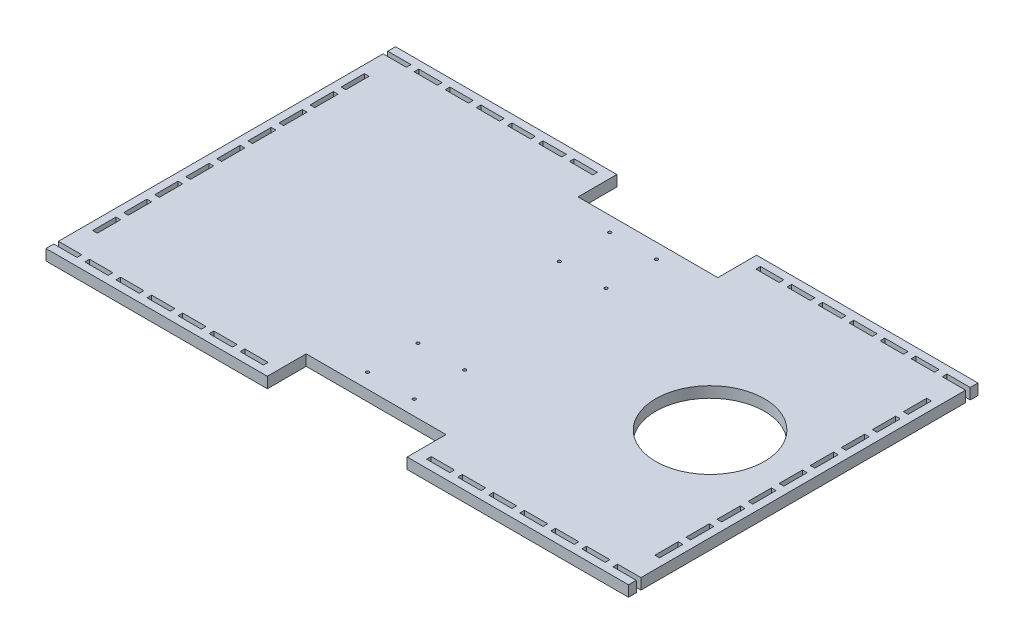
SolidWorks part; units mm, degrees
material "Thornel Mat VMA"
ref_plane "Front Plane" through (0, 0, 0) normal (0, 0, 1) x (1, 0, 0)
ref_plane "Top Plane" through (0, 0, 0) normal (0, 1, 0) x (1, 0, 0)
ref_plane "Right Plane" through (0, 0, 0) normal (1, 0, 0) x (0, 0, -1)
sketch "Sketch6" plane through (0, 0, 0) normal (0, 1, 0) x (1, 0, 0)
  line L0 (-187.5, 0) -> (187.5, 0) construction
  line L1 (-187.5, 112.5) -> (187.5, 112.5)
  line L2 (-187.5, 112.5) -> (-187.5, -112.5)
  line L3 (-187.5, -112.5) -> (187.5, -112.5)
  line L4 (187.5, 112.5) -> (187.5, -112.5)
  line L5 (0, -112.5) -> (0, -87.5) construction
  line L7 (187.5, -107.5) -> (172.5, -107.5)
  line L8 (187.5, -107.5) -> (187.5, -104.5)
  line L9 (187.5, -104.5) -> (172.5, -104.5)
  line L10 (172.5, -107.5) -> (172.5, -104.5)
  line L35 (187.5, 107.5) -> (172.5, 107.5)
  line L36 (187.5, 107.5) -> (187.5, 104.5)
  line L37 (187.5, 104.5) -> (172.5, 104.5)
  line L38 (172.5, 107.5) -> (172.5, 104.5)
  line L63 (-187.5, 104.5) -> (-172.5, 104.5)
  line L64 (-187.5, 104.5) -> (-187.5, 107.5)
  line L65 (-187.5, 107.5) -> (-172.5, 107.5)
  line L66 (-172.5, 104.5) -> (-172.5, 107.5)
  line L91 (-187.5, -107.5) -> (-172.5, -107.5)
  line L92 (-187.5, -107.5) -> (-187.5, -104.5)
  line L93 (-187.5, -104.5) -> (-172.5, -104.5)
  line L94 (-172.5, -107.5) -> (-172.5, -104.5)
  line L118 (167.5, 107.5) -> (152.5, 107.5)
  line L119 (152.5, 107.5) -> (152.5, 104.5)
  line L120 (167.5, 104.5) -> (152.5, 104.5)
  line L121 (167.5, 107.5) -> (167.5, 104.5)
  line L122 (167.5, -107.5) -> (152.5, -107.5)
  line L123 (152.5, -107.5) -> (152.5, -104.5)
  line L124 (167.5, -104.5) -> (152.5, -104.5)
  line L125 (167.5, -107.5) -> (167.5, -104.5)
  line L126 (147.5, 107.5) -> (132.5, 107.5)
  line L127 (132.5, 107.5) -> (132.5, 104.5)
  line L128 (147.5, 104.5) -> (132.5, 104.5)
  line L129 (147.5, 107.5) -> (147.5, 104.5)
  line L130 (147.5, -107.5) -> (132.5, -107.5)
  line L131 (132.5, -107.5) -> (132.5, -104.5)
  line L132 (147.5, -104.5) -> (132.5, -104.5)
  line L133 (147.5, -107.5) -> (147.5, -104.5)
  line L134 (127.5, 107.5) -> (112.5, 107.5)
  line L135 (112.5, 107.5) -> (112.5, 104.5)
  line L136 (127.5, 104.5) -> (112.5, 104.5)
  line L137 (127.5, 107.5) -> (127.5, 104.5)
  line L138 (127.5, -107.5) -> (112.5, -107.5)
  line L139 (112.5, -107.5) -> (112.5, -104.5)
  line L140 (127.5, -104.5) -> (112.5, -104.5)
  line L141 (127.5, -107.5) -> (127.5, -104.5)
  line L142 (107.5, 107.5) -> (92.5, 107.5)
  line L143 (92.5, 107.5) -> (92.5, 104.5)
  line L144 (107.5, 104.5) -> (92.5, 104.5)
  line L145 (107.5, 107.5) -> (107.5, 104.5)
  line L146 (107.5, -107.5) -> (92.5, -107.5)
  line L147 (92.5, -107.5) -> (92.5, -104.5)
  line L148 (107.5, -104.5) -> (92.5, -104.5)
  line L149 (107.5, -107.5) -> (107.5, -104.5)
  line L150 (87.5, 107.5) -> (72.5, 107.5)
  line L151 (72.5, 107.5) -> (72.5, 104.5)
  line L152 (87.5, 104.5) -> (72.5, 104.5)
  line L153 (87.5, 107.5) -> (87.5, 104.5)
  line L154 (87.5, -107.5) -> (72.5, -107.5)
  line L155 (72.5, -107.5) -> (72.5, -104.5)
  line L156 (87.5, -104.5) -> (72.5, -104.5)
  line L157 (87.5, -107.5) -> (87.5, -104.5)
  line L158 (67.5, 107.5) -> (52.5, 107.5)
  line L159 (52.5, 107.5) -> (52.5, 104.5)
  line L160 (67.5, 104.5) -> (52.5, 104.5)
  line L161 (67.5, 107.5) -> (67.5, 104.5)
  line L162 (67.5, -107.5) -> (52.5, -107.5)
  line L163 (52.5, -107.5) -> (52.5, -104.5)
  line L164 (67.5, -104.5) -> (52.5, -104.5)
  line L165 (67.5, -107.5) -> (67.5, -104.5)
  line L166 (-167.5, -107.5) -> (-152.5, -107.5)
  line L167 (-152.5, -107.5) -> (-152.5, -104.5)
  line L168 (-167.5, -104.5) -> (-152.5, -104.5)
  line L169 (-167.5, -107.5) -> (-167.5, -104.5)
  line L170 (-167.5, 104.5) -> (-152.5, 104.5)
  line L171 (-152.5, 104.5) -> (-152.5, 107.5)
  line L172 (-167.5, 107.5) -> (-152.5, 107.5)
  line L173 (-167.5, 104.5) -> (-167.5, 107.5)
  line L174 (-147.5, -107.5) -> (-132.5, -107.5)
  line L175 (-132.5, -107.5) -> (-132.5, -104.5)
  line L176 (-147.5, -104.5) -> (-132.5, -104.5)
  line L177 (-147.5, -107.5) -> (-147.5, -104.5)
  line L178 (-147.5, 104.5) -> (-132.5, 104.5)
  line L179 (-132.5, 104.5) -> (-132.5, 107.5)
  line L180 (-147.5, 107.5) -> (-132.5, 107.5)
  line L181 (-147.5, 104.5) -> (-147.5, 107.5)
  line L182 (-127.5, -107.5) -> (-112.5, -107.5)
  line L183 (-112.5, -107.5) -> (-112.5, -104.5)
  line L184 (-127.5, -104.5) -> (-112.5, -104.5)
  line L185 (-127.5, -107.5) -> (-127.5, -104.5)
  line L186 (-127.5, 104.5) -> (-112.5, 104.5)
  line L187 (-112.5, 104.5) -> (-112.5, 107.5)
  line L188 (-127.5, 107.5) -> (-112.5, 107.5)
  line L189 (-127.5, 104.5) -> (-127.5, 107.5)
  line L190 (-107.5, -107.5) -> (-92.5, -107.5)
  line L191 (-92.5, -107.5) -> (-92.5, -104.5)
  line L192 (-107.5, -104.5) -> (-92.5, -104.5)
  line L193 (-107.5, -107.5) -> (-107.5, -104.5)
  line L194 (-107.5, 104.5) -> (-92.5, 104.5)
  line L195 (-92.5, 104.5) -> (-92.5, 107.5)
  line L196 (-107.5, 107.5) -> (-92.5, 107.5)
  line L197 (-107.5, 104.5) -> (-107.5, 107.5)
  line L198 (-87.5, -107.5) -> (-72.5, -107.5)
  line L199 (-72.5, -107.5) -> (-72.5, -104.5)
  line L200 (-87.5, -104.5) -> (-72.5, -104.5)
  line L201 (-87.5, -107.5) -> (-87.5, -104.5)
  line L202 (-87.5, 104.5) -> (-72.5, 104.5)
  line L203 (-72.5, 104.5) -> (-72.5, 107.5)
  line L204 (-87.5, 107.5) -> (-72.5, 107.5)
  line L205 (-87.5, 104.5) -> (-87.5, 107.5)
  line L206 (-67.5, -107.5) -> (-52.5, -107.5)
  line L207 (-52.5, -107.5) -> (-52.5, -104.5)
  line L208 (-67.5, -104.5) -> (-52.5, -104.5)
  line L209 (-67.5, -107.5) -> (-67.5, -104.5)
  line L210 (-67.5, 104.5) -> (-52.5, 104.5)
  line L211 (-52.5, 104.5) -> (-52.5, 107.5)
  line L212 (-67.5, 107.5) -> (-52.5, 107.5)
  line L213 (-67.5, 104.5) -> (-67.5, 107.5)
  line L214 (0, -112.5) -> (0, -87.5) construction
  line L215 (45, -112.5) -> (-45, -112.5)
  line L216 (45, -112.5) -> (45, -87.5)
  line L217 (45, -87.5) -> (-45, -87.5)
  line L218 (-45, -112.5) -> (-45, -87.5)
  line L219 (45, 87.5) -> (-45, 87.5)
  line L220 (45, -100) -> (-45, -100) construction
  line L221 (-45, 112.5) -> (-45, 87.5)
  line L222 (45, 112.5) -> (-45, 112.5)
  line L223 (45, 112.5) -> (45, 87.5)
  line L224 (179.5, 0) -> (182.5, 0) construction
  line L225 (182.5, -7.5) -> (179.5, -7.5)
  line L226 (182.5, -7.5) -> (182.5, 7.5)
  line L227 (182.5, 7.5) -> (179.5, 7.5)
  line L228 (179.5, -7.5) -> (179.5, 7.5)
  line L229 (187.5, 0) -> (182.5, 0) construction
  line L230 (181, -7.5) -> (181, 7.5) construction
  line L231 (182.5, 12.5) -> (182.5, 27.5)
  line L232 (182.5, 12.5) -> (179.5, 12.5)
  line L233 (179.5, 12.5) -> (179.5, 27.5)
  line L234 (182.5, 27.5) -> (179.5, 27.5)
  line L235 (182.5, 32.5) -> (182.5, 47.5)
  line L236 (182.5, 32.5) -> (179.5, 32.5)
  line L237 (179.5, 32.5) -> (179.5, 47.5)
  line L238 (182.5, 47.5) -> (179.5, 47.5)
  line L239 (182.5, 52.5) -> (182.5, 67.5)
  line L240 (182.5, 52.5) -> (179.5, 52.5)
  line L241 (179.5, 52.5) -> (179.5, 67.5)
  line L242 (182.5, 67.5) -> (179.5, 67.5)
  line L243 (182.5, 72.5) -> (182.5, 87.5)
  line L244 (182.5, 72.5) -> (179.5, 72.5)
  line L245 (179.5, 72.5) -> (179.5, 87.5)
  line L246 (182.5, 87.5) -> (179.5, 87.5)
  line L247 (182.5, -7.5) -> (182.5, 7.5)
  line L248 (182.5, -7.5) -> (179.5, -7.5)
  line L249 (179.5, -7.5) -> (179.5, 7.5)
  line L250 (182.5, 7.5) -> (179.5, 7.5)
  line L251 (182.5, 12.5) -> (182.5, 27.5)
  line L252 (182.5, 12.5) -> (179.5, 12.5)
  line L253 (179.5, 12.5) -> (179.5, 27.5)
  line L254 (182.5, 27.5) -> (179.5, 27.5)
  line L255 (182.5, 32.5) -> (182.5, 47.5)
  line L256 (182.5, 32.5) -> (179.5, 32.5)
  line L257 (179.5, 32.5) -> (179.5, 47.5)
  line L258 (182.5, 47.5) -> (179.5, 47.5)
  line L259 (182.5, 52.5) -> (182.5, 67.5)
  line L260 (182.5, 52.5) -> (179.5, 52.5)
  line L261 (179.5, 52.5) -> (179.5, 67.5)
  line L262 (182.5, 67.5) -> (179.5, 67.5)
  line L263 (182.5, -27.5) -> (182.5, -12.5)
  line L264 (182.5, -27.5) -> (179.5, -27.5)
  line L265 (179.5, -27.5) -> (179.5, -12.5)
  line L266 (182.5, -12.5) -> (179.5, -12.5)
  line L267 (182.5, -7.5) -> (182.5, 7.5)
  line L268 (182.5, -7.5) -> (179.5, -7.5)
  line L269 (179.5, -7.5) -> (179.5, 7.5)
  line L270 (182.5, 7.5) -> (179.5, 7.5)
  line L271 (182.5, 12.5) -> (182.5, 27.5)
  line L272 (182.5, 12.5) -> (179.5, 12.5)
  line L273 (179.5, 12.5) -> (179.5, 27.5)
  line L274 (182.5, 27.5) -> (179.5, 27.5)
  line L275 (182.5, 32.5) -> (182.5, 47.5)
  line L276 (182.5, 32.5) -> (179.5, 32.5)
  line L277 (179.5, 32.5) -> (179.5, 47.5)
  line L278 (182.5, 47.5) -> (179.5, 47.5)
  line L279 (182.5, -47.5) -> (182.5, -32.5)
  line L280 (182.5, -47.5) -> (179.5, -47.5)
  line L281 (179.5, -47.5) -> (179.5, -32.5)
  line L282 (182.5, -32.5) -> (179.5, -32.5)
  line L283 (182.5, -27.5) -> (182.5, -12.5)
  line L284 (182.5, -27.5) -> (179.5, -27.5)
  line L285 (179.5, -27.5) -> (179.5, -12.5)
  line L286 (182.5, -12.5) -> (179.5, -12.5)
  line L287 (182.5, -7.5) -> (182.5, 7.5)
  line L288 (182.5, -7.5) -> (179.5, -7.5)
  line L289 (179.5, -7.5) -> (179.5, 7.5)
  line L290 (182.5, 7.5) -> (179.5, 7.5)
  line L291 (182.5, 12.5) -> (182.5, 27.5)
  line L292 (182.5, 12.5) -> (179.5, 12.5)
  line L293 (179.5, 12.5) -> (179.5, 27.5)
  line L294 (182.5, 27.5) -> (179.5, 27.5)
  line L295 (182.5, -67.5) -> (182.5, -52.5)
  line L296 (182.5, -67.5) -> (179.5, -67.5)
  line L297 (179.5, -67.5) -> (179.5, -52.5)
  line L298 (182.5, -52.5) -> (179.5, -52.5)
  line L299 (182.5, -47.5) -> (182.5, -32.5)
  line L300 (182.5, -47.5) -> (179.5, -47.5)
  line L301 (179.5, -47.5) -> (179.5, -32.5)
  line L302 (182.5, -32.5) -> (179.5, -32.5)
  line L303 (182.5, -27.5) -> (182.5, -12.5)
  line L304 (182.5, -27.5) -> (179.5, -27.5)
  line L305 (179.5, -27.5) -> (179.5, -12.5)
  line L306 (182.5, -12.5) -> (179.5, -12.5)
  line L307 (182.5, -7.5) -> (182.5, 7.5)
  line L308 (182.5, -7.5) -> (179.5, -7.5)
  line L309 (179.5, -7.5) -> (179.5, 7.5)
  line L310 (182.5, 7.5) -> (179.5, 7.5)
  line L311 (182.5, -27.5) -> (182.5, -12.5)
  line L312 (182.5, -27.5) -> (179.5, -27.5)
  line L313 (179.5, -27.5) -> (179.5, -12.5)
  line L314 (182.5, -12.5) -> (179.5, -12.5)
  line L315 (182.5, -47.5) -> (182.5, -32.5)
  line L316 (182.5, -47.5) -> (179.5, -47.5)
  line L317 (179.5, -47.5) -> (179.5, -32.5)
  line L318 (182.5, -32.5) -> (179.5, -32.5)
  line L319 (182.5, -67.5) -> (182.5, -52.5)
  line L320 (182.5, -67.5) -> (179.5, -67.5)
  line L321 (179.5, -67.5) -> (179.5, -52.5)
  line L322 (182.5, -52.5) -> (179.5, -52.5)
  line L323 (182.5, -87.5) -> (182.5, -72.5)
  line L324 (182.5, -87.5) -> (179.5, -87.5)
  line L325 (179.5, -87.5) -> (179.5, -72.5)
  line L326 (182.5, -72.5) -> (179.5, -72.5)
  line L327 (-179.5, 0) -> (-182.5, 0) construction
  line L328 (-179.5, 7.5) -> (-182.5, 7.5)
  line L329 (-179.5, 7.5) -> (-179.5, -7.5)
  line L330 (-179.5, -7.5) -> (-182.5, -7.5)
  line L331 (-182.5, 7.5) -> (-182.5, -7.5)
  line L332 (-187.5, 0) -> (-182.5, 0) construction
  line L333 (-181, 7.5) -> (-181, -7.5) construction
  line L334 (-179.5, 27.5) -> (-179.5, 12.5)
  line L335 (-179.5, 27.5) -> (-182.5, 27.5)
  line L336 (-182.5, 27.5) -> (-182.5, 12.5)
  line L337 (-179.5, 12.5) -> (-182.5, 12.5)
  line L338 (-179.5, 47.5) -> (-179.5, 32.5)
  line L339 (-179.5, 47.5) -> (-182.5, 47.5)
  line L340 (-182.5, 47.5) -> (-182.5, 32.5)
  line L341 (-179.5, 32.5) -> (-182.5, 32.5)
  line L342 (-179.5, 67.5) -> (-179.5, 52.5)
  line L343 (-179.5, 67.5) -> (-182.5, 67.5)
  line L344 (-182.5, 67.5) -> (-182.5, 52.5)
  line L345 (-179.5, 52.5) -> (-182.5, 52.5)
  line L346 (-179.5, 87.5) -> (-179.5, 72.5)
  line L347 (-179.5, 87.5) -> (-182.5, 87.5)
  line L348 (-182.5, 87.5) -> (-182.5, 72.5)
  line L349 (-179.5, 72.5) -> (-182.5, 72.5)
  line L350 (-179.5, 7.5) -> (-179.5, -7.5)
  line L351 (-179.5, 7.5) -> (-182.5, 7.5)
  line L352 (-182.5, 7.5) -> (-182.5, -7.5)
  line L353 (-179.5, -7.5) -> (-182.5, -7.5)
  line L354 (-179.5, 27.5) -> (-179.5, 12.5)
  line L355 (-179.5, 27.5) -> (-182.5, 27.5)
  line L356 (-182.5, 27.5) -> (-182.5, 12.5)
  line L357 (-179.5, 12.5) -> (-182.5, 12.5)
  line L358 (-179.5, 47.5) -> (-179.5, 32.5)
  line L359 (-179.5, 47.5) -> (-182.5, 47.5)
  line L360 (-182.5, 47.5) -> (-182.5, 32.5)
  line L361 (-179.5, 32.5) -> (-182.5, 32.5)
  line L362 (-179.5, 67.5) -> (-179.5, 52.5)
  line L363 (-179.5, 67.5) -> (-182.5, 67.5)
  line L364 (-182.5, 67.5) -> (-182.5, 52.5)
  line L365 (-179.5, 52.5) -> (-182.5, 52.5)
  line L366 (-179.5, -12.5) -> (-179.5, -27.5)
  line L367 (-179.5, -12.5) -> (-182.5, -12.5)
  line L368 (-182.5, -12.5) -> (-182.5, -27.5)
  line L369 (-179.5, -27.5) -> (-182.5, -27.5)
  line L370 (-179.5, 7.5) -> (-179.5, -7.5)
  line L371 (-179.5, 7.5) -> (-182.5, 7.5)
  line L372 (-182.5, 7.5) -> (-182.5, -7.5)
  line L373 (-179.5, -7.5) -> (-182.5, -7.5)
  line L374 (-179.5, 27.5) -> (-179.5, 12.5)
  line L375 (-179.5, 27.5) -> (-182.5, 27.5)
  line L376 (-182.5, 27.5) -> (-182.5, 12.5)
  line L377 (-179.5, 12.5) -> (-182.5, 12.5)
  line L378 (-179.5, 47.5) -> (-179.5, 32.5)
  line L379 (-179.5, 47.5) -> (-182.5, 47.5)
  line L380 (-182.5, 47.5) -> (-182.5, 32.5)
  line L381 (-179.5, 32.5) -> (-182.5, 32.5)
  line L382 (-179.5, -32.5) -> (-179.5, -47.5)
  line L383 (-179.5, -32.5) -> (-182.5, -32.5)
  line L384 (-182.5, -32.5) -> (-182.5, -47.5)
  line L385 (-179.5, -47.5) -> (-182.5, -47.5)
  line L386 (-179.5, -12.5) -> (-179.5, -27.5)
  line L387 (-179.5, -12.5) -> (-182.5, -12.5)
  line L388 (-182.5, -12.5) -> (-182.5, -27.5)
  line L389 (-179.5, -27.5) -> (-182.5, -27.5)
  line L390 (-179.5, 7.5) -> (-179.5, -7.5)
  line L391 (-179.5, 7.5) -> (-182.5, 7.5)
  line L392 (-182.5, 7.5) -> (-182.5, -7.5)
  line L393 (-179.5, -7.5) -> (-182.5, -7.5)
  line L394 (-179.5, 27.5) -> (-179.5, 12.5)
  line L395 (-179.5, 27.5) -> (-182.5, 27.5)
  line L396 (-182.5, 27.5) -> (-182.5, 12.5)
  line L397 (-179.5, 12.5) -> (-182.5, 12.5)
  line L398 (-179.5, -52.5) -> (-179.5, -67.5)
  line L399 (-179.5, -52.5) -> (-182.5, -52.5)
  line L400 (-182.5, -52.5) -> (-182.5, -67.5)
  line L401 (-179.5, -67.5) -> (-182.5, -67.5)
  line L402 (-179.5, -32.5) -> (-179.5, -47.5)
  line L403 (-179.5, -32.5) -> (-182.5, -32.5)
  line L404 (-182.5, -32.5) -> (-182.5, -47.5)
  line L405 (-179.5, -47.5) -> (-182.5, -47.5)
  line L406 (-179.5, -12.5) -> (-179.5, -27.5)
  line L407 (-179.5, -12.5) -> (-182.5, -12.5)
  line L408 (-182.5, -12.5) -> (-182.5, -27.5)
  line L409 (-179.5, -27.5) -> (-182.5, -27.5)
  line L410 (-179.5, 7.5) -> (-179.5, -7.5)
  line L411 (-179.5, 7.5) -> (-182.5, 7.5)
  line L412 (-182.5, 7.5) -> (-182.5, -7.5)
  line L413 (-179.5, -7.5) -> (-182.5, -7.5)
  line L414 (-179.5, -12.5) -> (-179.5, -27.5)
  line L415 (-179.5, -12.5) -> (-182.5, -12.5)
  line L416 (-182.5, -12.5) -> (-182.5, -27.5)
  line L417 (-179.5, -27.5) -> (-182.5, -27.5)
  line L418 (-179.5, -32.5) -> (-179.5, -47.5)
  line L419 (-179.5, -32.5) -> (-182.5, -32.5)
  line L420 (-182.5, -32.5) -> (-182.5, -47.5)
  line L421 (-179.5, -47.5) -> (-182.5, -47.5)
  line L422 (-179.5, -52.5) -> (-179.5, -67.5)
  line L423 (-179.5, -52.5) -> (-182.5, -52.5)
  line L424 (-182.5, -52.5) -> (-182.5, -67.5)
  line L425 (-179.5, -67.5) -> (-182.5, -67.5)
  line L426 (-179.5, -72.5) -> (-179.5, -87.5)
  line L427 (-179.5, -72.5) -> (-182.5, -72.5)
  line L428 (-182.5, -72.5) -> (-182.5, -87.5)
  line L429 (-179.5, -87.5) -> (-182.5, -87.5)
  line L430 (0, 0) -> (0, 112.5) construction
  line L432 (-15, -45.52) -> (15, -45.52) construction
  line L433 (45, 87.5) -> (45, 61.72) construction
  line L434 (45, 61.72) -> (15, 61.72) construction
  line L435 (15, -45.52) -> (15, -77.92) construction
  line L439 (15, -61.72) -> (45, -87.5) construction
  line L440 (45, -87.5) -> (45, -61.72) construction
  line L441 (45, -61.72) -> (15, -61.72) construction
  line L444 (-15, -45.52) -> (-16, -45.52) construction
  line L445 (15, 61.72) -> (15, 45.52) construction
  line L446 (15, 45.52) -> (-15, 45.52) construction
  line L448 (-15, -45.52) -> (-15, -77.92) construction
  line L449 (-15, -77.92) -> (-16, -77.92) construction
  line L450 (15, 77.92) -> (-15, 77.92) construction
  line L451 (-15, 77.92) -> (-15, 45.52) construction
  line L452 (-15, -77.92) -> (15, -77.92) construction
  line L453 (15, 77.92) -> (15, 61.72) construction
  line L454 (15, 61.72) -> (45, 87.5) construction
  circle A0 centre (127.5, 0) radius 35
  circle A1 centre (15, -45.52) radius 1
  circle A2 centre (-15, -45.52) radius 1
  circle A3 centre (-15, -77.92) radius 1
  circle A4 centre (15, -77.92) radius 1
  circle A5 centre (-15, 45.52) radius 1
  circle A6 centre (-15, 77.92) radius 1
  circle A7 centre (15, 77.92) radius 1
  circle A8 centre (15, 45.52) radius 1
  circle A10 centre (-172, 0) radius 1.5 construction
  point P8 (0, 0)
  point P372 (0, 0)
  dimension "D3" = 70
  dimension "D38" = 2
  dimension "D43" = 3
  dimension "D1" = 375
  dimension "D2" = 225
  dimension "D4" = 15
  dimension "D5" = 5
  dimension "D6" = 3
  dimension "D7" = 3
  dimension "D8" = 5
  dimension "D9" = 15
  dimension "D10" = 3
  dimension "D11" = 15
  dimension "D12" = 5
  dimension "D13" = 3
  dimension "D14" = 15
  dimension "D15" = 5
  dimension "D16" = 60
  dimension "D19" = 5
  dimension "D20" = 5
  dimension "D21" = 90
  dimension "D22" = 25
  dimension "D23" = 3
  dimension "D24" = 15
  dimension "D25" = 5
  dimension "D28" = 5
  dimension "D29" = 5
  dimension "D30" = 3
  dimension "D31" = 15
  dimension "D32" = 5
  dimension "D35" = 5
  dimension "D36" = 5
  dimension "D37" = 25.78
  dimension "D39" = 32.4
  dimension "D40" = 30
  dimension "D41" = 30
  dimension "D42" = 16.2
  dimension "D44" = 7.5
  dimension "D17" = 7
  dimension "D18" = 7
  dimension "D26" = 5
  dimension "D27" = 5
  dimension "D33" = 5
  dimension "D34" = 5
extrude "Boss-Extrude3" add sketch "Sketch6" along normal blind 7 contours L94 L91 L2 L3 L4 L7 L10 L9 L37 L38 L35 L1 L65 L66 L63 L93 A0 L137 L141 L129 L133 L121 L125 region at (-6.6369, 0, 0)
